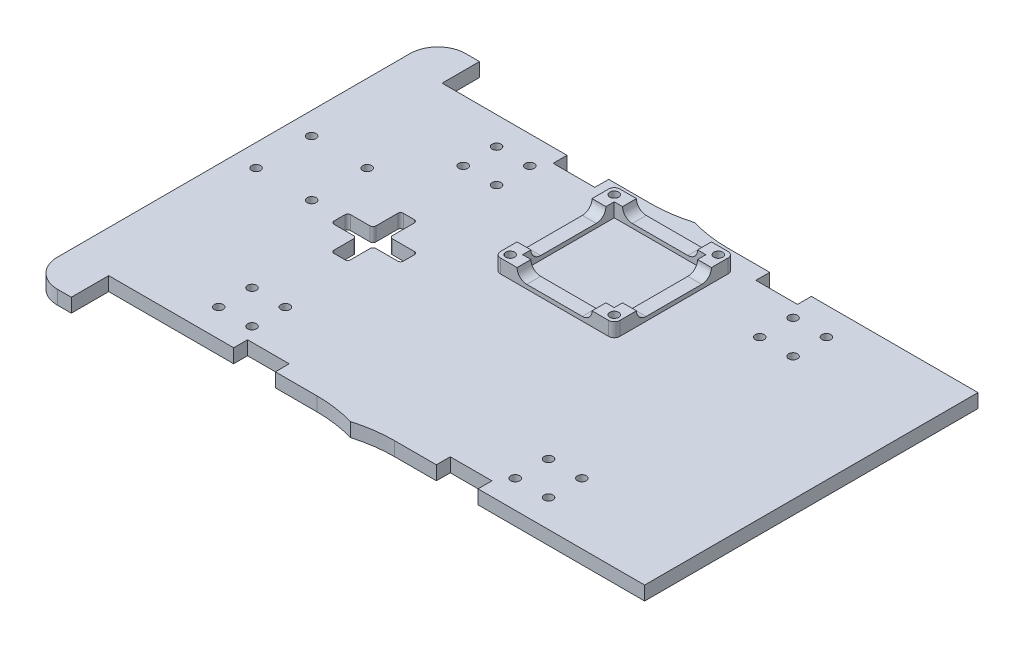
SolidWorks part; units mm, degrees
ref_plane "Front Plane" through (0, 0, 0) normal (0, 0, 1) x (1, 0, 0)
ref_plane "Top Plane" through (0, 0, 0) normal (0, 1, 0) x (1, 0, 0)
ref_plane "Right Plane" through (0, 0, 0) normal (1, 0, 0) x (0, 0, -1)
sketch "Sketch1" plane through (0, 0, 0) normal (0, 1, 0) x (1, 0, 0)
  line L1 (104, 73.5) -> (-104, 73.5)
  line L2 (104, 73.5) -> (104, -73.5)
  line L3 (104, -73.5) -> (-104, -73.5)
  line L4 (-104, 73.5) -> (-104, -73.5)
  line L5 (104, 73.5) -> (-104, -73.5) construction
  line L6 (104, -73.5) -> (-104, 73.5) construction
  point P0 (0, 0)
  dimension "D1" = 208
  dimension "D2" = 147
extrude "Boss-Extrude1" add sketch "Sketch1" along normal blind 5
sketch "Sketch2" plane through (0, 5, 0) normal (0, 1, 0) x (1, 0, 0)
  line L0 (-89, 80.0276) -> (-89, 60.0276)
  line L1 (-89, 60.0276) -> (-44, 60.0276)
  line L2 (-44, 60.0276) -> (-44, 55.0276)
  line L3 (-44, 55.0276) -> (-29, 55.0276)
  line L4 (-29, 55.0276) -> (-29, 60.0276)
  line L5 (-29, 60.0276) -> (-14, 60.0276)
  line L8 (0, 62.0276) -> (0, 82.0276)
  line L9 (0, 82.0276) -> (-89, 82.0276)
  line L10 (-89, 82.0276) -> (-89, 80.0276)
  line L11 (-104, 73.5) -> (-104, -73.5) construction
  arc A0 (-14, 60.0276) -> (0, 62.0276) centre (-14, 110.0276) ccw
  dimension "D6" = 50
  dimension "D1" = 20
  dimension "D2" = 45
  dimension "D3" = 15
  dimension "D4" = 5
  dimension "D5" = 15
  dimension "D7" = 20
  dimension "D8" = 89
  dimension "D9" = 15
extrude "Cut-Extrude2" cut sketch "Sketch2" against normal through all
mirror "Mirror1" about plane through (0, 0, 0) normal (0, 0, 1) of "Cut-Extrude2"
mirror "Mirror2" about plane through (0, 0, 0) normal (1, 0, 0) of "Mirror1"
fillet "Fillet1" radius 10 4 edges at (104, 2.5, 73.5) (104, 2.5, -73.5) (-104, 2.5, -73.5) (-104, 2.5, 73.5)
sketch "Sketch3" plane through (0, 5, 0) normal (0, 1, 0) x (1, 0, 0)
  line L0 (-56.3946, -4.4571) -> (-56.3946, -11.5383)
  line L1 (-55.3946, 12.4617) -> (-51.3946, 12.4617)
  line L2 (-56.3946, 11.4617) -> (-56.3946, 3.5429)
  line L3 (-55.3946, -12.5383) -> (-51.3946, -12.5383)
  line L4 (-50.3946, 11.4617) -> (-50.3946, 3.5429)
  line L7 (-41.4758, 2.5429) -> (-49.3946, 2.5429)
  line L8 (-40.4758, 1.5429) -> (-40.4758, -2.4571)
  line L9 (-41.4758, -3.4571) -> (-49.3946, -3.4571)
  line L10 (-65.4758, 1.5429) -> (-65.4758, -2.4571)
  line L16 (-50.3946, -4.4571) -> (-50.3946, -11.5383)
  line L18 (-57.3946, 2.5429) -> (-64.4758, 2.5429)
  line L19 (-57.3946, -3.4571) -> (-64.4758, -3.4571)
  arc A0 (-50.3946, -4.4571) -> (-49.3946, -3.4571) centre (-49.3946, -4.4571) cw
  arc A1 (-56.3946, -4.4571) -> (-57.3946, -3.4571) centre (-57.3946, -4.4571) ccw
  arc A2 (-50.3946, 3.5429) -> (-49.3946, 2.5429) centre (-49.3946, 3.5429) ccw
  arc A3 (-56.3946, 3.5429) -> (-57.3946, 2.5429) centre (-57.3946, 3.5429) cw
  arc A4 (-41.4758, 2.5429) -> (-40.4758, 1.5429) centre (-41.4758, 1.5429) cw
  arc A5 (-40.4758, -2.4571) -> (-41.4758, -3.4571) centre (-41.4758, -2.4571) cw
  arc A6 (-51.3946, -12.5383) -> (-50.3946, -11.5383) centre (-51.3946, -11.5383) ccw
  arc A7 (-56.3946, -11.5383) -> (-55.3946, -12.5383) centre (-55.3946, -11.5383) ccw
  arc A8 (-64.4758, -3.4571) -> (-65.4758, -2.4571) centre (-64.4758, -2.4571) cw
  arc A9 (-64.4758, 2.5429) -> (-65.4758, 1.5429) centre (-64.4758, 1.5429) ccw
  arc A10 (-51.3946, 12.4617) -> (-50.3946, 11.4617) centre (-51.3946, 11.4617) cw
  arc A11 (-55.3946, 12.4617) -> (-56.3946, 11.4617) centre (-55.3946, 11.4617) ccw
  point P0 (-52.9758, -0.0383)
  point P5 (-52.9758, -0.0383)
  point P16 (-56.3946, -3.4571)
  point P23 (-56.3946, 2.5429)
  point P30 (-50.3946, -12.5383)
  point P39 (-50.3946, 12.4617)
  dimension "D2" = 1
  dimension "D1" = 25
  dimension "D3" = 4
extrude "Cut-Extrude3" cut sketch "Sketch3" against normal through all
sketch "Sketch5" plane through (0, 5, 0) normal (0, 1, 0) x (1, 0, 0)
  line L0 (-104, 63.5) -> (-104, -63.5) construction
  line L2 (-104, 0) -> (104, 0) construction
  line L3 (-104, 63.5) -> (-104, -63.5) construction
  line L4 (104, -63.5) -> (104, 63.5) construction
  line L6 (-96, 0.0398) -> (-76, 0.0398) construction
  line L7 (-96, 0.0398) -> (-96, 20.0398) construction
  line L8 (-96, 20.0398) -> (-76, 20.0398) construction
  line L9 (-76, 0.0398) -> (-76, 20.0398) construction
  line L10 (-96, 0.0398) -> (-76, 20.0398) construction
  line L11 (-96, 20.0398) -> (-76, 0.0398) construction
  circle A0 centre (-96, 20.0398) radius 1.6
  circle A1 centre (-76, 20.0398) radius 1.6
  circle A2 centre (-76, 0.0398) radius 1.6
  circle A3 centre (-96, 0.0398) radius 1.6
  point P11 (-86, 10.0398)
  dimension "D1" = 20
  dimension "D4" = 3.2
  dimension "D5" = 3.2
  dimension "D6" = 3.2
  dimension "D7" = 3.2
  dimension "D2" = 20
  dimension "D3" = 8
extrude "Cut-Extrude4" cut sketch "Sketch5" against normal blind 10
sketch "Sketch8" plane through (0, 5, 0) normal (0, 1, 0) x (1, 0, 0)
  line L0 (-53.3946, 12.4617) -> (-53.3946, -52.7767) construction
  line L1 (-51.3946, 12.4617) -> (-55.3946, 12.4617) construction
  line L2 (-59.3946, -38.0276) -> (-47.3946, -38.0276) construction
  line L7 (-47.3946, -38.0276) -> (-47.3946, -50.0276) construction
  line L8 (-47.3946, -50.0276) -> (-59.3946, -50.0276) construction
  line L9 (-59.3946, -50.0276) -> (-59.3946, -38.0276) construction
  line L10 (-47.3946, -38.0276) -> (-47.3946, -37.2065)
  line L11 (-59.3946, -38.0276) -> (-53.3946, -44.0276) construction
  line L12 (-53.3946, -44.0276) -> (-47.3946, -50.0276) construction
  line L13 (-59.3946, -50.0276) -> (-53.3946, -44.0276) construction
  line L14 (-53.3946, -44.0276) -> (-47.3946, -38.0276) construction
  line L15 (-104, 0) -> (104, 0) construction
  line L16 (-104, 63.5) -> (-104, -63.5) construction
  line L17 (104, -63.5) -> (104, 63.5) construction
  line L18 (0, 62.0276) -> (0, -62.0276) construction
  circle A0 centre (-59.3946, -50.0276) radius 1.6
  circle A1 centre (-47.3946, -50.0276) radius 1.6
  circle A2 centre (-47.3946, -38.0276) radius 1.6
  circle A3 centre (-59.3946, -38.0276) radius 1.6
  circle A4 centre (-59.3946, 50.0276) radius 1.6
  circle A5 centre (-47.3946, 50.0276) radius 1.6
  circle A6 centre (-47.3946, 38.0276) radius 1.6
  circle A7 centre (-59.3946, 38.0276) radius 1.6
  circle A8 centre (59.3946, 50.0276) radius 1.6
  circle A9 centre (47.3946, 50.0276) radius 1.6
  circle A10 centre (47.3946, 38.0276) radius 1.6
  circle A11 centre (59.3946, 38.0276) radius 1.6
  circle A12 centre (47.3946, -50.0276) radius 1.6
  circle A13 centre (47.3946, -38.0276) radius 1.6
  circle A14 centre (59.3946, -50.0276) radius 1.6
  circle A15 centre (59.3946, -38.0276) radius 1.6
  point P4 (-53.3946, -44.0276)
  dimension "D4" = 3.2
  dimension "D5" = 3.2
  dimension "D6" = 3.2
  dimension "D7" = 3.2
  dimension "D1" = 12
  dimension "D2" = 12
  dimension "D3" = 5
extrude "Cut-Extrude5" cut sketch "Sketch8" against normal blind 10 contours A3 | A2 | A0 | A1 | A13 | A12 | A14 | A15 | A6 | A7 | A4 | A5 | A9 | A10 | A11 | A8
sketch "Sketch9" plane through (0, 5, 0) normal (0, 1, 0) x (1, 0, 0)
  line L0 (-65.4758, -0.4571) -> (-11.2396, -0.4571) construction
  line L1 (-65.4758, 1.5429) -> (-65.4758, -2.4571) construction
  line L3 (-21, 11.0276) -> (22, 11.0276)
  line L4 (-21, 11.0276) -> (-21, 54.0276)
  line L5 (-21, 54.0276) -> (22, 54.0276)
  line L6 (22, 11.0276) -> (22, 54.0276)
  line L8 (-29, 60.0276) -> (-14, 60.0276) construction
  line L9 (-29, 55.0276) -> (-29, 60.0276) construction
  line L10 (-16, 16.0276) -> (-16, 49.0276)
  line L11 (-16, 49.0276) -> (17, 49.0276)
  line L12 (17, 16.0276) -> (17, 49.0276)
  line L13 (-16, 16.0276) -> (17, 16.0276)
  dimension "D1" = 43
  dimension "D2" = 43
  dimension "D3" = 6
  dimension "D4" = 8
  dimension "D5" = 5
extrude "Boss-Extrude3" add sketch "Sketch9" along normal blind 5
sketch "Sketch10" plane through (0, 0, -11.0276) normal (0, 0, 1) x (1, 0, 0)
  line L0 (-13, 10) -> (-13, 6.5)
  line L1 (-21, 10) -> (22, 10) construction
  line L2 (-13, 6.5) -> (14, 6.5)
  line L3 (14, 6.5) -> (14, 10)
  line L4 (14, 10) -> (-13, 10)
  dimension "D1" = 8
  dimension "D2" = 8
  dimension "D3" = 3.5
extrude "Cut-Extrude6" cut sketch "Sketch10" against normal blind 62
sketch "Sketch11" plane through (22, 0, 0) normal (1, 0, 0) x (0, 0, -1)
  line L0 (11.0276, 10) -> (54.0276, 10) construction
  line L1 (19.0276, 10) -> (46.0276, 10)
  line L2 (19.0276, 10) -> (19.0276, 6.5)
  line L3 (19.0276, 6.5) -> (46.0276, 6.5)
  line L4 (46.0276, 10) -> (46.0276, 6.5)
  dimension "D1" = 8
  dimension "D2" = 8
  dimension "D3" = 3.5
extrude "Cut-Extrude7" cut sketch "Sketch11" against normal blind 62
fillet "Fillet4" radius 3.5 6 edges at (19.5, 6.5, -19.0276) (19.5, 6.5, -46.0276) (14, 6.5, -51.5276) (-18.5, 6.5, -19.0276) (-18.5, 6.5, -46.0276) (-13, 6.5, -13.5276)
ref_plane "Plane1" through (0, 10, 0) normal (0, 1, 0) x (1, 0, 0)
sketch "Sketch12" plane through (0, 10, 0) normal (0, 1, 0) x (1, 0, 0)
  line L0 (22, 54.0276) -> (-21, 54.0276) construction
  line L1 (0.5, 54.0276) -> (0.5, 10.5061) construction
  line L2 (-21, 54.0276) -> (-21, 11.0276) construction
  line L3 (-21, 32.5276) -> (22.9972, 32.5276) construction
  circle A0 centre (-18.25, 51.2776) radius 2.75 construction
  circle A1 centre (-18.25, 51.2776) radius 1.6
  circle A2 centre (19.25, 51.2776) radius 1.6
  circle A3 centre (19.25, 13.7776) radius 1.6
  circle A4 centre (-18.25, 13.7776) radius 1.6
  dimension "D1" = 5.5
  dimension "D2" = 3.2
extrude "Cut-Extrude8" cut sketch "Sketch12" against normal blind 62
fillet "Fillet5" radius 3.5 2 edges at (14, 6.5, -13.5276) (-13, 6.5, -51.5276)
fillet "Fillet6" radius 2 4 edges at (-21, 7.5, -54.0276) (22, 7.5, -54.0276) (-21, 7.5, -11.0276) (22, 7.5, -11.0276)
sketch "Sketch13" plane through (0, 5, 0) normal (0, 1, 0) x (1, 0, 0)
sketch "Sketch14" plane through (0, 5, 0) normal (0, 1, 0) x (1, 0, 0)
  line L0 (89, 60.0276) -> (104, 60.0276)
  line L1 (104, -63.5) -> (104, 63.5) construction
  line L4 (89, 73.5) -> (89, 60.0276)
  line L5 (89, -60.0276) -> (89, -73.5)
  line L6 (89, -73.5) -> (104, -73.5)
  line L7 (104, -73.5) -> (104, -60.0276)
  line L8 (89, -60.0276) -> (104, -60.0276)
  line L9 (104, 60.0276) -> (104, 73.5)
  line L10 (104, 73.5) -> (89, 73.5)
extrude "Cut-Extrude10" cut sketch "Sketch14" against normal blind 10
